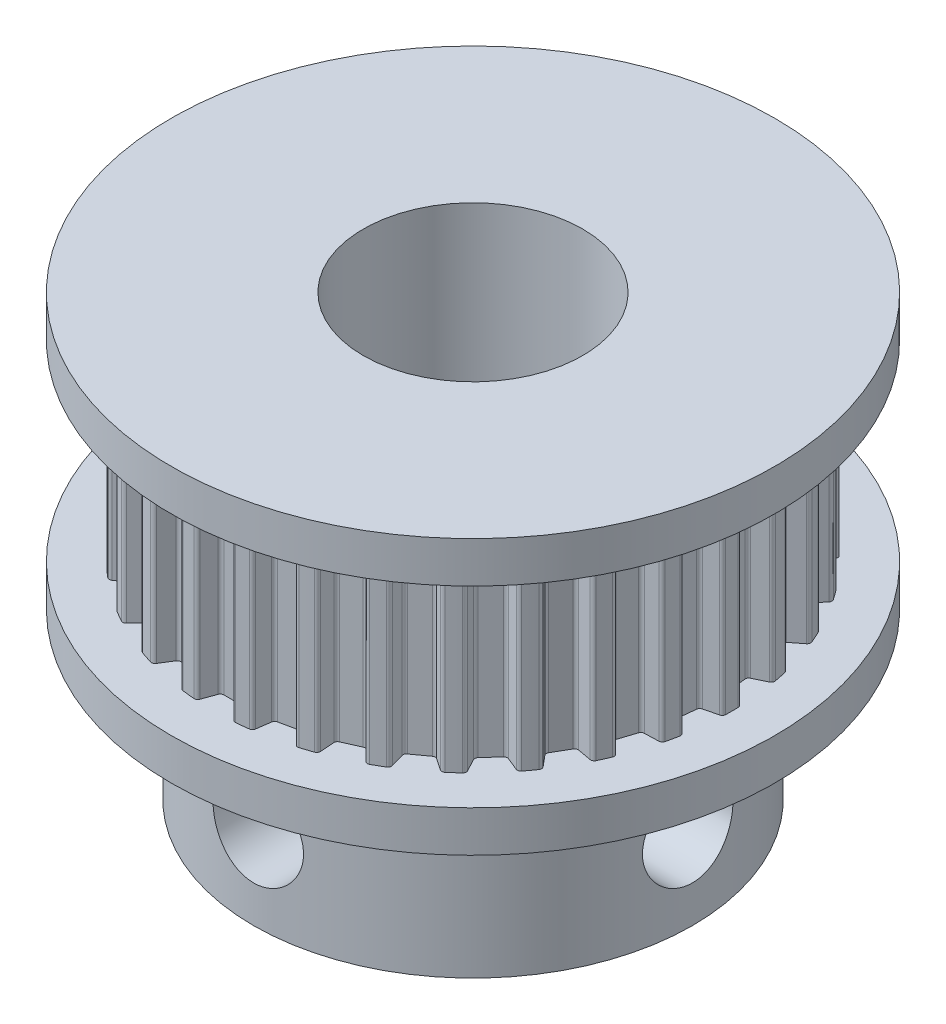
SolidWorks part; units mm, degrees
ref_plane "Front Plane" through (0, 0, 0) normal (0, 0, 1) x (1, 0, 0)
ref_plane "Top Plane" through (0, 0, 0) normal (0, 1, 0) x (1, 0, 0)
ref_plane "Right Plane" through (0, 0, 0) normal (1, 0, 0) x (0, 0, -1)
sketch "草圖1" plane through (0, 0, 0) normal (0, 1, 0) x (1, 0, 0)
  circle A0 centre (0, 0) radius 9.445
  dimension "D1" = 18.89
extrude "填料-伸長1" add sketch "草圖1" along normal blind 3.5 and the other way blind 3.5 contours A0
sketch "草圖2" plane through (0, -3.5, 0) normal (0, -1, 0) x (1, 0, 0)
  line L0 (0, 9.445) -> (0, 0) construction
  line L1 (0, 8.755) -> (-0.42, 8.755)
  line L2 (-0.42, 8.755) -> (-0.6627, 9.4217)
  line L3 (0, 8.755) -> (0.42, 8.755)
  line L4 (0.42, 8.755) -> (0.6627, 9.4217)
  circle A0 centre (0, 0) radius 9.445 construction
  arc A1 (-0.6627, 9.4217) -> (0.6627, 9.4217) centre (0, 0) cw
  circle M7 centre (0, 0) radius 9.445
  dimension "D1" = 0.69
  dimension "D2" = 0.84
  dimension "D3" = 40
extrude "除料-伸長1" cut sketch "草圖2" against normal through all contours L0 A1 L2 L1 | L0 L3 L4 M7 region at (0.2745, -3.5, 9.1221) region at (-0.2745, -3.5, 9.1221)
fillet "圓角1" radius 0.13 4 edges at (-0.6627, 0, 9.4217) (0.6627, 0, 9.4217) (0.42, 0, 8.755) (-0.42, 0, 8.755)
pattern_circular "環狀複製排列1" count 30 over 360 about axis through (0, -3.5, 0) along (0, 1, 0) of "圓角1", "除料-伸長1"
sketch "草圖3" plane through (0, 3.5, 0) normal (0, 1, 0) x (1, 0, 0)
  circle A0 centre (0, 0) radius 11
  dimension "D1" = 22
extrude "填料-伸長2" add sketch "草圖3" along normal blind 1.5
sketch "草圖4" plane through (0, -3.5, 0) normal (0, -1, 0) x (1, 0, 0)
  circle A0 centre (0, 0) radius 11
  circle A1 centre (0, 0) radius 11 construction
extrude "填料-伸長3" add sketch "草圖4" along normal blind 1.5
sketch "草圖10" plane through (0, -5, 0) normal (0, -1, 0) x (1, 0, 0)
  circle A0 centre (0, 0) radius 8
  dimension "D1" = 16
extrude "填料-伸長4" add sketch "草圖10" along normal blind 6
sketch "草圖5" plane through (0, -5, 0) normal (0, -1, 0) x (1, 0, 0)
  circle A0 centre (0, 0) radius 4
  dimension "D1" = 8
extrude "除料-伸長2" cut sketch "草圖5" against normal through all and the other way through all
hole_wizard "M4x0.7 螺紋孔1" positions "草圖8" profile "草圖9" tap size "M4x0.7" standard "Ansi Metric" end condition through all
sketch "草圖8" plane through (0, 0, 0) normal (0, 0, 1) x (1, 0, 0)
  line L0 (0, -8) -> (0, -11) construction
  line L1 (-8, -11) -> (8, -11) construction
  point P15 (0, -8)
  dimension "D1" = 3
sketch "草圖9" plane through (0, -8, 0) normal (1, 0, 0) x (0, 1, 0)
  line L0 (0, 0) -> (0, 11)
  line L1 (0, 11) -> (1.65, 11)
  line L2 (1.65, 11) -> (1.65, 0)
  line L5 (1.65, 0) -> (0, 0)
  line L11 (0, -6.35) -> (0, 107.95) construction
  dimension "貫穿螺孔鑽直徑" = 3.3
  dimension "貫穿螺孔鑽深度" = 11
pattern_circular "環狀複製排列2" count 2 over 90 about axis through (0, 5, 0) along (0, -1, 0) of "M4x0.7 螺紋孔1" reverse direction yes
